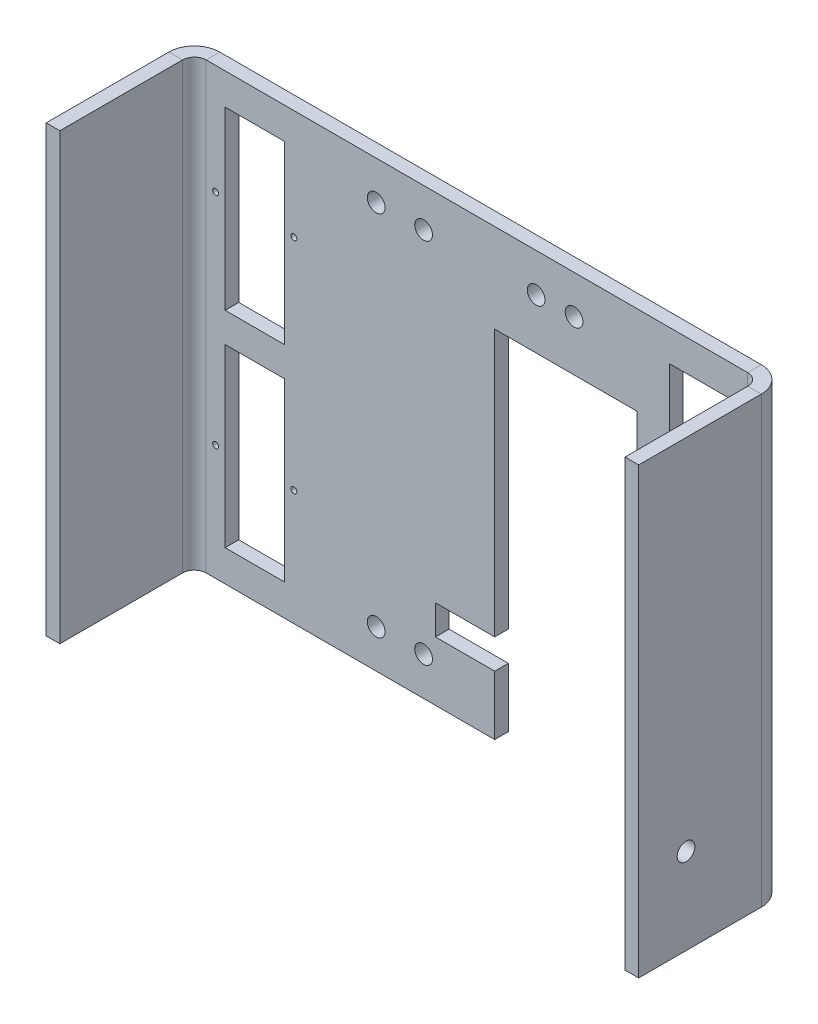
SolidWorks part; units mm, degrees
note: The reader was unsure of these and kept them because the rebuilt part matched: flange length of "Edge-Flange1", "Edge-Flange2".
ref_plane "Front Plane" through (0, 0, 0) normal (0, 0, 1) x (1, 0, 0)
ref_plane "Top Plane" through (0, 0, 0) normal (0, 1, 0) x (1, 0, 0)
ref_plane "Right Plane" through (0, 0, 0) normal (1, 0, 0) x (0, 0, -1)
sketch "Sketch2" plane through (0, 0, 0) normal (0, 0, 1) x (1, 0, 0)
  line L1 (0, 0) -> (100, 0)
  line L2 (0, 0) -> (0, 75)
  line L3 (0, 75) -> (100, 75)
  line L4 (100, 0) -> (100, 75)
  line L5 (0, 0) -> (100, 75) construction
  line L6 (0, 75) -> (100, 0) construction
  point P4 (50, 37.5)
  dimension "D1" = 75
  dimension "D2" = 100
base flange "Base-Flange1" sketch "Sketch2" thickness 2.3 reverse thickness direction no parameters "D1"=2
edge flange "Edge-Flange1" sketch "Sketch9" flange angle 90 flange length 25 flange position material inside bend radius 2 thickness 2.3 relief rectangular parameters "D6"=10
sketch "Sketch9" plane through (0, 0, 0) normal (-1, 0, 0) x (0, -1, 0)
  line L2 (-75, 0) -> (-75, 22.7)
  line L3 (-75, 22.7) -> (0, 22.7)
  line L4 (0, 22.7) -> (0, 0)
  line L7 (-75, 0) -> (0, 0) construction
  line L8 (-75, 0) -> (0, 0)
bend "EdgeBend1" bend radius 2 bend angle 90 parameters "D5"=1
edge flange "Edge-Flange2" sketch "Sketch12" flange angle 90 flange length 25 flange position material inside bend radius 2 thickness 2.3 relief rectangular parameters "D6"=10
sketch "Sketch12" plane through (100, 0, 0) normal (1, 0, 0) x (0, 1, 0)
  line L2 (0, 0) -> (0, 22.7)
  line L3 (0, 22.7) -> (75, 22.7)
  line L4 (75, 22.7) -> (75, 0)
  line L7 (0, 0) -> (75, 0) construction
  line L8 (0, 0) -> (75, 0)
bend "EdgeBend2" bend radius 2 bend angle 90 parameters "D5"=2
sketch "Sketch13" plane through (0, 0, -2.3) normal (0, 0, -1) x (-1, 0, 0)
  line L0 (-4.3, 0) -> (-95.7, 0) construction
  line L1 (-77, 0) -> (-53, 0)
  line L2 (-77, 0) -> (-77, 60)
  line L3 (-77, 60) -> (-53, 60)
  line L4 (-53, 0) -> (-53, 10)
  line L5 (-77, 0) -> (-53, 60) construction
  line L6 (-77, 60) -> (-53, 0) construction
  line L7 (-100, 75) -> (-100, 0) construction
  line L8 (-95.7, 75) -> (-4.3, 75) construction
  line L9 (-53, 15) -> (-43, 15)
  line L10 (-43, 15) -> (-43, 10)
  line L11 (-43, 10) -> (-53, 10)
  line L13 (-53, 15) -> (-53, 60)
  line L14 (-50, 75) -> (-50, 0) construction
  line L15 (-92.5, 69.7) -> (-82.5, 69.7)
  line L16 (-92.5, 69.7) -> (-92.5, 5.3)
  line L17 (-92.5, 5.3) -> (-82.5, 5.3)
  line L18 (-82.5, 69.7) -> (-82.5, 5.3)
  line L19 (-92.5, 69.7) -> (-82.5, 5.3) construction
  line L20 (-92.5, 5.3) -> (-82.5, 69.7) construction
  line L21 (-7.5, 5.3) -> (-17.5, 5.3)
  line L22 (-17.5, 69.7) -> (-17.5, 5.3)
  line L23 (-7.5, 69.7) -> (-17.5, 69.7)
  line L24 (-7.5, 69.7) -> (-7.5, 5.3)
  line L25 (0, 37.5) -> (-100, 37.5) construction
  line L26 (0, 0) -> (0, 75) construction
  circle A0 centre (-66.4, 68.5) radius 1.5
  circle A1 centre (-60, 68.5) radius 1.5
  circle A2 centre (-41, 68.5) radius 1.5
  circle A3 centre (-33, 68.5) radius 1.5
  circle A4 centre (-41, 6.5) radius 1.5
  circle A5 centre (-33, 6.5) radius 1.5
  point P4 (-65, 30)
  point P19 (-87.5, 37.5)
  dimension "D16" = 3
  dimension "D17" = 3
  dimension "D18" = 3
  dimension "D19" = 3
  dimension "D1" = 23
  dimension "D2" = 24
  dimension "D3" = 15
  dimension "D4" = 10
  dimension "D5" = 10
  dimension "D6" = 5
  dimension "D7" = 5.3
  dimension "D8" = 7.5
  dimension "D9" = 17.5
  dimension "D10" = 5.3
  dimension "D11" = 33.6
  dimension "D12" = 40
  dimension "D13" = 59
  dimension "D14" = 67
  dimension "D15" = 6.5
extrude "Cut-Extrude1" cut sketch "Sketch13" against normal up to next normal cut yes
sketch "Sketch14" plane through (0, 0, -2.3) normal (0, 0, -1) x (-1, 0, 0)
  line L0 (-82.5, 5.3) -> (-82.5, 69.7) construction
  line L1 (-92.5, 69.7) -> (-92.5, 5.3) construction
  line L2 (-82.5, 40) -> (-92.5, 40)
  line L3 (-82.5, 40) -> (-82.5, 35)
  line L4 (-82.5, 35) -> (-92.5, 35)
  line L5 (-92.5, 40) -> (-92.5, 35)
  line L6 (-82.5, 40) -> (-92.5, 35) construction
  line L7 (-82.5, 35) -> (-92.5, 40) construction
  line L8 (-7.5, 5.3) -> (-7.5, 69.7) construction
  line L9 (-7.5, 40) -> (-17.5, 40)
  line L10 (-7.5, 40) -> (-7.5, 35)
  line L11 (-7.5, 35) -> (-17.5, 35)
  line L12 (-17.5, 40) -> (-17.5, 35)
  line L13 (-7.5, 40) -> (-17.5, 35) construction
  line L14 (-7.5, 35) -> (-17.5, 40) construction
  line L15 (-17.5, 69.7) -> (-17.5, 5.3) construction
  point P6 (-87.5, 37.5)
  point P13 (-12.5, 37.5)
  point P18 (-82.5, 37.5)
  point P19 (-7.5, 37.5)
  point P20 (-82.5, 37.5)
  point P22 (-7.5, 37.5)
  dimension "D1" = 5
  dimension "D2" = 5
base flange "Tab1" sketch "Sketch14" thickness 2.3 reverse thickness direction no parameters "D1"=2
sketch "Sketch17" plane through (0, 0, -2.3) normal (0, 0, -1) x (-1, 0, 0)
  line L0 (-95.7, 75) -> (-4.3, 75) construction
  line L1 (-92.5, 69.7) -> (-92.5, 40) construction
  line L2 (-92.5, 35) -> (-92.5, 5.3) construction
  line L3 (-87.5, 69.7) -> (-87.5, 5.3) construction
  line L4 (-82.5, 69.7) -> (-92.5, 69.7) construction
  line L5 (-92.5, 5.3) -> (-82.5, 5.3) construction
  line L6 (-50, 75) -> (-50, 0) construction
  line L7 (-4.3, 0) -> (-53, 0) construction
  circle A0 centre (-94.1, 56.5) radius 0.5
  circle A1 centre (-94.1, 19.5) radius 0.5
  circle A2 centre (-80.9, 19.5) radius 0.5
  circle A3 centre (-80.9, 56.5) radius 0.5
  circle A4 centre (-19.1, 19.5) radius 0.5
  circle A5 centre (-5.9, 19.5) radius 0.5
  circle A6 centre (-5.9, 56.5) radius 0.5
  circle A7 centre (-19.1, 56.5) radius 0.5
  dimension "D3" = 1
  dimension "D4" = 1
  dimension "D1" = 18.5
  dimension "D2" = 37
  dimension "D5" = 1.6
  dimension "D6" = 1.6
extrude "Cut-Extrude2" cut sketch "Sketch17" against normal up to next normal cut yes
sketch "Sketch18" plane through (100, 0, 0) normal (1, 0, 0) x (0, 0, -1)
  line L0 (-22.7, 75) -> (-22.7, 0) construction
  line L1 (-22.7, 0) -> (-2, 0) construction
  circle A0 centre (-14.7, 14.5) radius 1.5
  dimension "D1" = 3
  dimension "D2" = 8
  dimension "D3" = 14.5
extrude "Cut-Extrude3" cut sketch "Sketch18" against normal up to next normal cut yes
sketch "Bend-Lines1" [suppressed] plane through (0, 0, 0) normal (0, 1, 0) x (1, 0, 0)
sketch "Bounding-Box1" [suppressed] plane through (0, 0, 0) normal (0, 1, 0) x (1, 0, 0)
sheet metal parameters "Sheet-Metal1" thickness 2.3 parameters "D1"=2
flat pattern "Flat-Pattern1" [suppressed]
sketch "Bend-Lines2" plane through (0, 0, 0) normal (0, 1, 0) x (1, 0, 0)
sketch3d "Bounding-Box2" [suppressed]
  line L0 (0, 0, 0) -> (-100, 0, 0) construction
  line L1 (0, 75, 0) -> (-100, 75, 0) construction
  line L2 (0, 0, 0) -> (0, 75, 0) construction
  line L3 (-100, 0, 0) -> (-100, 75, 0) construction
sheet metal parameters "Sheet-Metal2" thickness 2.3 parameters "D1"=2
flat pattern "Flat-Pattern1"
sketch "Bend-Lines2" plane through (0, 0, 0) normal (0, 0, 1) x (1, 0, 0)
  line L0 (1.826, 75) -> (1.826, 0) construction
  line L1 (1.826, 75) -> (1.826, 0) construction
sketch3d "Bounding-Box2" [suppressed]
  line L0 (-21.348, 0, 0) -> (100, 0, 0) construction
  line L1 (-21.348, 75, 0) -> (100, 75, 0) construction
  line L2 (-21.348, 0, 0) -> (-21.348, 75, 0) construction
  line L3 (100, 0, 0) -> (100, 75, 0) construction
bend of the flat pattern "Flatten-<EdgeBend1>1"
sheet metal parameters "Sheet-Metal3" thickness 2.3 parameters "D1"=2
flat pattern "Flat-Pattern1"
sketch "Bend-Lines2" plane through (0, 0, 0) normal (0, 0, 1) x (1, 0, 0)
  line L0 (1.826, 75) -> (1.826, 0) construction
  line L1 (1.826, 75) -> (1.826, 0) construction
  line L2 (98.174, 0) -> (98.174, 75) construction
  line L3 (98.174, 0) -> (98.174, 75) construction
sketch3d "Bounding-Box2" [suppressed]
  line L0 (-21.348, 0, 0) -> (121.348, 0, 0) construction
  line L1 (-21.348, 75, 0) -> (121.348, 75, 0) construction
  line L2 (-21.348, 0, 0) -> (-21.348, 75, 0) construction
  line L3 (121.348, 0, 0) -> (121.348, 75, 0) construction
bend of the flat pattern "Flatten-<EdgeBend1>1"
bend of the flat pattern "Flatten-<EdgeBend2>1"
sheet metal parameters "Sheet-Metal4" thickness 2.3 parameters "D1"=2
flat pattern "Flat-Pattern1"
sketch "Bend-Lines2" plane through (0, 0, 0) normal (0, 0, 1) x (1, 0, 0)
  line L0 (1.826, 75) -> (1.826, 0) construction
  line L1 (1.826, 75) -> (1.826, 0) construction
  line L2 (98.174, 0) -> (98.174, 75) construction
  line L3 (98.174, 0) -> (98.174, 75) construction
sketch3d "Bounding-Box2" [suppressed]
  line L0 (-21.348, 0, 0) -> (121.348, 0, 0) construction
  line L1 (-21.348, 75, 0) -> (121.348, 75, 0) construction
  line L2 (-21.348, 0, 0) -> (-21.348, 75, 0) construction
  line L3 (121.348, 0, 0) -> (121.348, 75, 0) construction
bend of the flat pattern "Flatten-<EdgeBend1>1"
bend of the flat pattern "Flatten-<EdgeBend2>1"
sheet metal parameters "Sheet-Metal5" thickness 2.3 parameters "D1"=2
flat pattern "Flat-Pattern5"
sketch "Bend-Lines3" plane through (0, 0, 0) normal (0, 0, 1) x (1, 0, 0)
  line L0 (98.174, 0) -> (98.174, 75) construction
  line L1 (1.826, 75) -> (1.826, 0) construction
  line L2 (98.174, 0) -> (98.174, 75) construction
  line L3 (1.826, 75) -> (1.826, 0) construction
sketch3d "Bounding-Box3" [suppressed]
  line L0 (-21.348, 0, 0) -> (121.348, 0, 0) construction
  line L1 (-21.348, 75, 0) -> (121.348, 75, 0) construction
  line L2 (-21.348, 0, 0) -> (-21.348, 75, 0) construction
  line L3 (121.348, 0, 0) -> (121.348, 75, 0) construction
bend of the flat pattern "Flatten-<EdgeBend2>2"
bend of the flat pattern "Flatten-<EdgeBend1>2"
sheet metal parameters "Sheet-Metal6" thickness 2.3 parameters "D1"=2
flat pattern "Flat-Pattern5"
sketch "Bend-Lines3" plane through (0, 0, 0) normal (0, 0, 1) x (1, 0, 0)
  line L0 (98.174, 0) -> (98.174, 75) construction
  line L1 (1.826, 75) -> (1.826, 0) construction
  line L2 (98.174, 0) -> (98.174, 75) construction
  line L3 (1.826, 75) -> (1.826, 0) construction
sketch3d "Bounding-Box3" [suppressed]
  line L0 (-21.348, 0, 0) -> (121.348, 0, 0) construction
  line L1 (-21.348, 75, 0) -> (121.348, 75, 0) construction
  line L2 (-21.348, 0, 0) -> (-21.348, 75, 0) construction
  line L3 (121.348, 0, 0) -> (121.348, 75, 0) construction
bend of the flat pattern "Flatten-<EdgeBend2>2"
bend of the flat pattern "Flatten-<EdgeBend1>2"
sheet metal parameters "Sheet-Metal7" thickness 2.3 parameters "D1"=2
flat pattern "Flat-Pattern5"
sketch "Bend-Lines3" plane through (0, 0, 0) normal (0, 0, 1) x (1, 0, 0)
  line L0 (98.174, 0) -> (98.174, 75) construction
  line L1 (1.826, 75) -> (1.826, 0) construction
  line L2 (98.174, 0) -> (98.174, 75) construction
  line L3 (1.826, 75) -> (1.826, 0) construction
sketch3d "Bounding-Box3" [suppressed]
  line L0 (-21.348, 0, 0) -> (121.348, 0, 0) construction
  line L1 (-21.348, 75, 0) -> (121.348, 75, 0) construction
  line L2 (-21.348, 0, 0) -> (-21.348, 75, 0) construction
  line L3 (121.348, 0, 0) -> (121.348, 75, 0) construction
bend of the flat pattern "Flatten-<EdgeBend2>2"
bend of the flat pattern "Flatten-<EdgeBend1>2"
